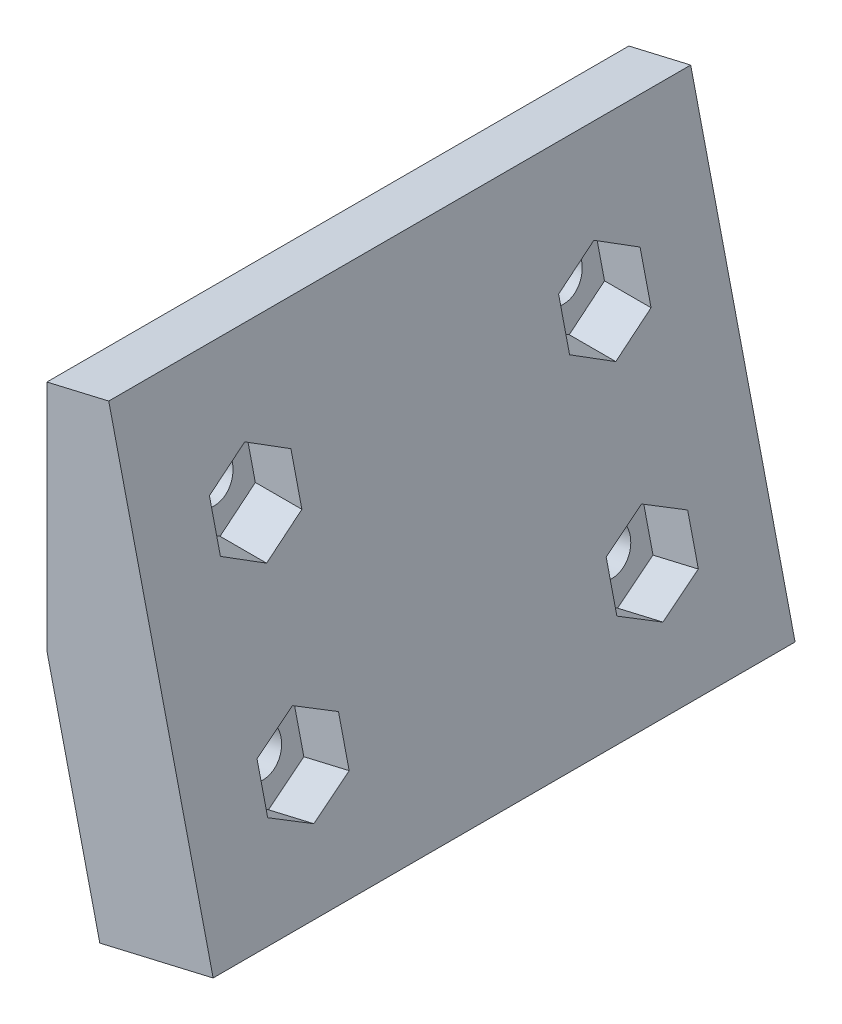
SolidWorks part; units mm, degrees
material "ABS"
ref_plane "Front Plane" through (0, 0, 0) normal (0, 0, 1) x (1, 0, 0)
ref_plane "Top Plane" through (0, 0, 0) normal (0, 1, 0) x (1, 0, 0)
ref_plane "Right Plane" through (0, 0, 0) normal (1, 0, 0) x (0, 0, -1)
sketch "Sketch1" plane through (0, 0, 0) normal (0, 0, 1) x (1, 0, 0)
  line L0 (0, -105.5) -> (0, -125.5)
  line L1 (0, -125.5) -> (0, 24.5) construction
  line L2 (0, -125.5) -> (4.5442, -144.9769)
  line L3 (0, -125.5) -> (21.7, -218.5082) construction
  line L4 (4.5442, -144.9769) -> (14.2827, -142.7048)
  line L5 (14.2827, -142.7048) -> (5.3131, -104.2604)
  line L6 (5.3131, -104.2604) -> (0, -105.5)
  dimension "D1" = 20
  dimension "D2" = 20
  dimension "D3" = 10
extrude "Boss-Extrude1" add sketch "Sketch1" against normal blind 50
sketch "Sketch2" plane through (0, 0, 0) normal (-1, 0, 0) x (0, 0, 1)
  line L0 (-50, -115.5) -> (0, -115.5) construction
  line L1 (-50, -105.5) -> (0, -105.5)
  line L2 (-50, -105.5) -> (-50, -125.5)
  line L3 (-50, -125.5) -> (0, -125.5)
  line L4 (0, -105.5) -> (0, -125.5)
  line L5 (-50, -105.5) -> (0, -125.5) construction
  line L6 (-50, -125.5) -> (0, -105.5) construction
  line L7 (-25, -105.5) -> (-25, -125.5) construction
  line L8 (-40, -111.4585) -> (-43.5, -113.4793)
  line L9 (-43.5, -113.4793) -> (-43.5, -117.5207)
  line L10 (-43.5, -117.5207) -> (-40, -119.5415)
  line L11 (-40, -119.5415) -> (-36.5, -117.5207)
  line L12 (-36.5, -117.5207) -> (-36.5, -113.4793)
  line L13 (-36.5, -113.4793) -> (-40, -111.4585)
  line L20 (-13.5, -113.4793) -> (-10, -111.4585)
  line L21 (-13.5, -117.5207) -> (-13.5, -113.4793)
  line L22 (-10, -119.5415) -> (-13.5, -117.5207)
  line L23 (-6.5, -117.5207) -> (-10, -119.5415)
  line L24 (-6.5, -113.4793) -> (-6.5, -117.5207)
  line L25 (-10, -111.4585) -> (-6.5, -113.4793)
  circle A0 centre (-40, -115.5) radius 3.5 construction
  circle A1 centre (-40, -115.5) radius 2
  circle A2 centre (-10, -115.5) radius 3.5 construction
  circle A3 centre (-10, -115.5) radius 2
  point P4 (-25, -115.5)
  dimension "D1" = 4
  dimension "D2" = 7
  dimension "D3" = 15
extrude "Cut-Extrude1" cut sketch "Sketch2" against normal blind 50 contours A1 | A3 region at (0, -115.5, -40) region at (0, -115.5, -10)
extrude "Cut-Extrude2" cut sketch "Sketch2<3>" along normal blind 4 from surface contours L12 L13 L8 L9 L10 L11 A1 | L25 L20 L21 L22 L23 L24 A3 region at (0, -112.5615, -38.3035) region at (0, -112.5615, -11.6965) starting at face at (7.4688, -113.5, -10)
sketch "Sketch2<3>" plane through (0, 0, 0) normal (-1, 0, 0) x (0, 0, 1) same geometry as "Sketch2"
sketch "Sketch3" plane through (-27.7691, -6.4789, 0) normal (-0.9738, -0.2272, 0) x (0, 0, 1)
  line L0 (0, -132.2176) -> (-50, -132.2176) construction
  line L1 (-50, -122.2176) -> (0, -122.2176)
  line L2 (-50, -122.2176) -> (-50, -142.2176)
  line L3 (-50, -142.2176) -> (0, -142.2176)
  line L4 (0, -122.2176) -> (0, -142.2176)
  line L5 (-50, -122.2176) -> (0, -142.2176) construction
  line L6 (-50, -142.2176) -> (0, -122.2176) construction
  line L7 (-25, -122.2176) -> (-25, -142.2176) construction
  line L8 (-40, -128.1762) -> (-43.5, -130.1969)
  line L9 (-43.5, -130.1969) -> (-43.5, -134.2384)
  line L10 (-43.5, -134.2384) -> (-40, -136.2591)
  line L11 (-40, -136.2591) -> (-36.5, -134.2384)
  line L12 (-36.5, -134.2384) -> (-36.5, -130.1969)
  line L13 (-36.5, -130.1969) -> (-40, -128.1762)
  line L14 (-13.5, -130.1969) -> (-10, -128.1762)
  line L15 (-13.5, -134.2384) -> (-13.5, -130.1969)
  line L16 (-10, -136.2591) -> (-13.5, -134.2384)
  line L17 (-6.5, -134.2384) -> (-10, -136.2591)
  line L18 (-6.5, -130.1969) -> (-6.5, -134.2384)
  line L19 (-10, -128.1762) -> (-6.5, -130.1969)
  circle A0 centre (-40, -132.2176) radius 2
  circle A1 centre (-40, -132.2176) radius 3.5 construction
  circle A2 centre (-10, -132.2176) radius 3.5 construction
  circle A3 centre (-10, -132.2176) radius 2
  point P4 (-25, -132.2176)
  dimension "D1" = 10
  dimension "D3" = 4
  dimension "D2" = 7
extrude "Cut-Extrude3" cut sketch "Sketch3" against normal through all contours A0 | A3 region at (2.2721, -135.2385, -40) region at (2.2721, -135.2385, -10)
extrude "Cut-Extrude4" cut sketch "Sketch3<3>" along normal blind 4 from surface contours L12 L13 L8 L9 L10 L11 A0 | L19 L14 L15 L16 L17 L18 A3 region at (1.6044, -132.3768, -38.3035) region at (1.6044, -132.3768, -11.6965) starting at face at (11.5561, -131.0187, -10)
sketch "Sketch3<3>" plane through (-27.7691, -6.4789, 0) normal (-0.9738, -0.2272, 0) x (0, 0, 1) same geometry as "Sketch3"
